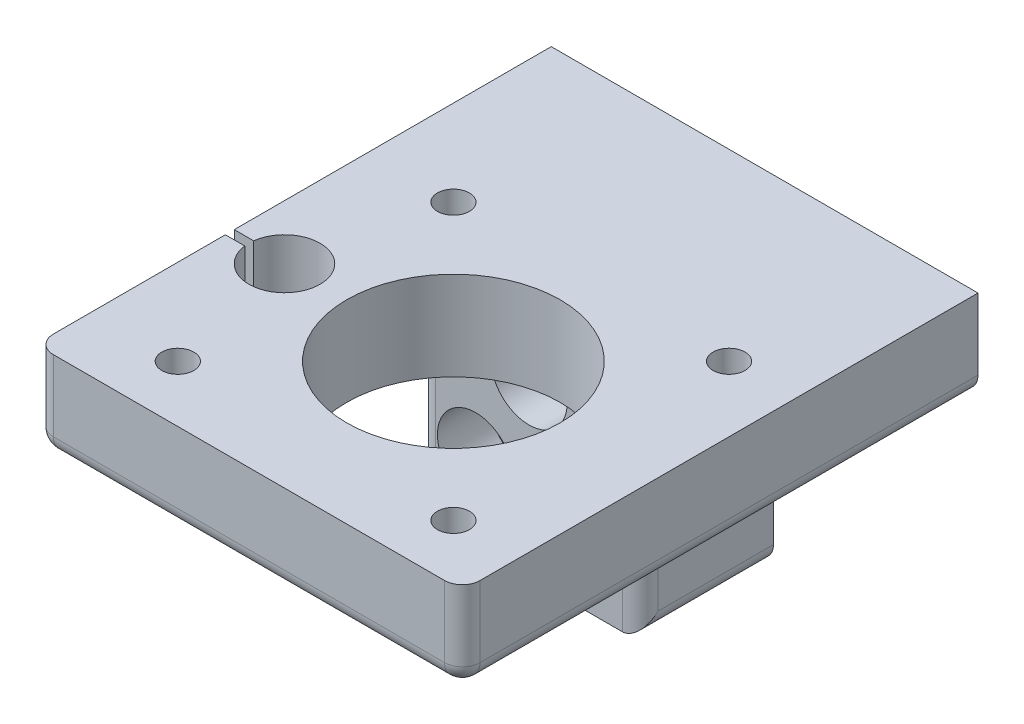
SolidWorks part; units mm, degrees
ref_plane "Front Plane" through (0, 0, 0) normal (0, 0, 1) x (1, 0, 0)
ref_plane "Top Plane" through (0, 0, 0) normal (0, 1, 0) x (1, 0, 0)
ref_plane "Right Plane" through (0, 0, 0) normal (1, 0, 0) x (0, 0, -1)
sketch "Sketch1" plane through (0, 0, 0) normal (0, 1, 0) x (1, 0, 0)
  line L0 (25.15, -36.15) -> (6.15, -36.15) construction
  line L1 (0, 0) -> (48, 0)
  line L2 (0, 0) -> (0, -58)
  line L3 (0, -58) -> (48, -58)
  line L4 (48, 0) -> (48, -58)
  line L5 (40.65, -20.65) -> (9.65, -20.65) construction
  line L6 (9.65, -20.65) -> (9.65, -51.65) construction
  line L7 (9.65, -51.65) -> (40.65, -51.65) construction
  line L8 (40.65, -51.65) -> (40.65, -20.65) construction
  line L9 (0, -35.65) -> (2.1814, -35.65)
  line L10 (2.1814, -35.65) -> (2.1814, -36.65)
  line L11 (2.1814, -36.65) -> (0, -36.65)
  line L12 (2.1814, -36.15) -> (6.15, -36.15) construction
  circle A1 centre (6.15, -36.15) radius 4
  circle A2 centre (25.15, -36.15) radius 12
  circle A5 centre (9.65, -20.65) radius 1.8
  circle A6 centre (9.65, -51.65) radius 1.8
  circle A7 centre (40.65, -51.65) radius 1.8
  circle A8 centre (40.65, -20.65) radius 1.8
  dimension "D3" = 8
  dimension "D4" = 24
  dimension "D6" = 3.5
  dimension "D7" = 22.85
  dimension "D8" = 3.6
  dimension "D10" = 6.35
  dimension "D1" = 48
  dimension "D2" = 58
  dimension "D5" = 21.85
  dimension "D9" = 31
  dimension "D11" = 7.35
  dimension "D12" = 1
extrude "Boss-Extrude1" add sketch "Sketch1" along normal blind 10 contours L4 L1 L2 L3 region at (24, 0, 0.7529)
sketch "Sketch2" plane through (0, 0, 0) normal (-1, 0, 0) x (0, 0, 1)
  line L1 (0, 0) -> (15, 0)
  line L2 (0, 0) -> (0, -28)
  line L3 (0, -28) -> (15, -28)
  line L4 (15, 0) -> (15, -28)
  dimension "D1" = 28
  dimension "D2" = 15
extrude "Boss-Extrude2" add sketch "Sketch2" against normal blind 25
sketch "Sketch3" plane through (0, 0, 15) normal (0, 0, 1) x (1, 0, 0)
  line L0 (12.5, -8.8038) -> (6.5, -19.1962) construction
  line L1 (6.5, -19.1962) -> (18.5, -19.1962) construction
  line L2 (18.5, -19.1962) -> (12.5, -8.8038) construction
  line L3 (12.5, -19.1962) -> (12.5, -28) construction
  line L4 (25, -28) -> (0, -28) construction
  line L5 (12.5, -8.8038) -> (12.5, 0) construction
  line L6 (25, 0) -> (0, 0) construction
  circle A0 centre (12.5, -8.8038) radius 2.8
  circle A1 centre (6.5, -19.1962) radius 2.8
  circle A2 centre (18.5, -19.1962) radius 2.8
  dimension "D1" = 5.6
  dimension "D2" = 12
extrude "Cut-Extrude1" cut sketch "Sketch3" against normal up to surface (15 mm away) up to face at (24.3333, -6, 0)
sketch "Sketch4" plane through (0, 0, 15) normal (0, 0, 1) x (1, 0, 0)
  circle A0 centre (12.5, -8.8038) radius 4.3
  circle A1 centre (6.5, -19.1962) radius 4.3
  circle A2 centre (18.5, -19.1962) radius 4.3
  dimension "D1" = 8.6
extrude "Cut-Extrude2" cut sketch "Sketch4" against normal blind 6
fillet "Fillet1" radius 2 10 edges at (48, 0, 29) (25, -14, 15) (24, 0, 58) (0, 0, 47.325) (0, 0, 25.325) (0, -14, 15) (0, -28, 7.5) (25, -28, 7.5) (48, 5, 58) (0, 5, 58)
